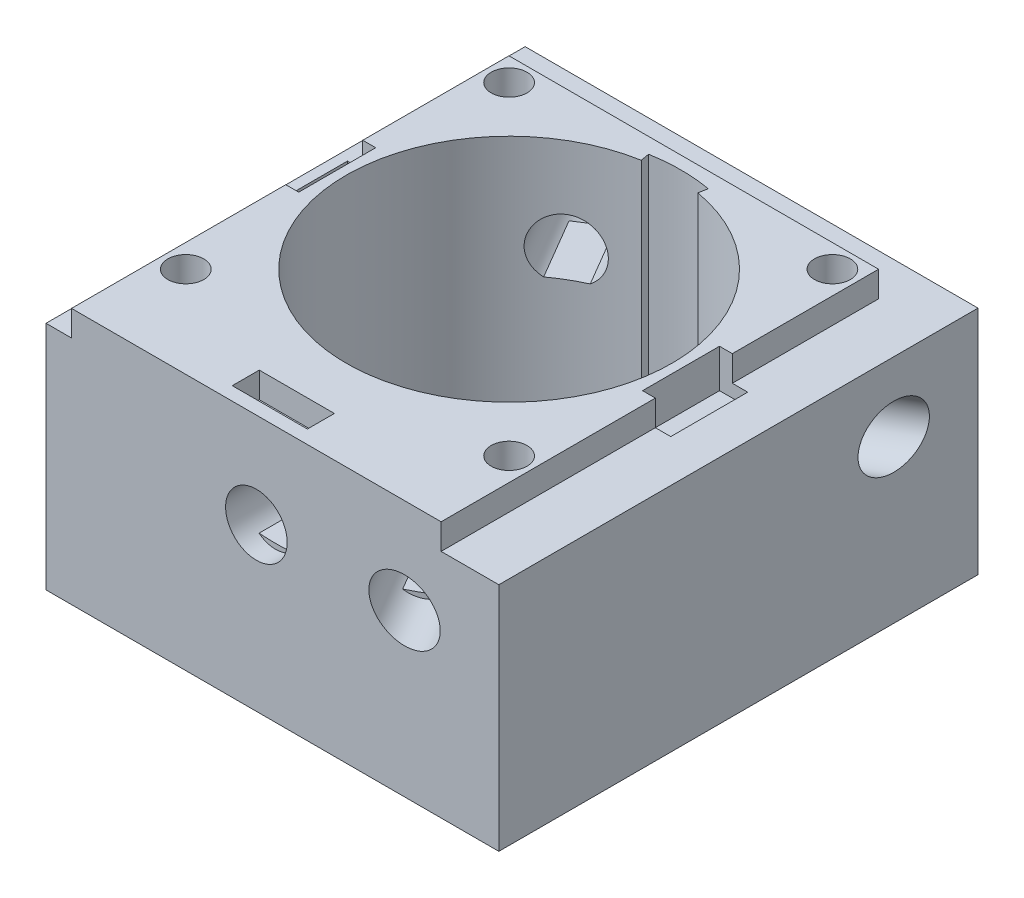
SolidWorks part; units mm, degrees
ref_plane "Front Plane" through (0, 0, 0) normal (0, 0, 1) x (1, 0, 0)
ref_plane "Top Plane" through (0, 0, 0) normal (0, 1, 0) x (1, 0, 0)
ref_plane "Right Plane" through (0, 0, 0) normal (1, 0, 0) x (0, 0, -1)
sketch "Sketch1" plane through (0, 0, 0) normal (0, 1, 0) x (1, 0, 0)
  line L1 (-20.828, 22.9235) -> (20.828, 22.9235)
  line L2 (-20.828, 22.9235) -> (-20.828, -22.9235)
  line L3 (-20.828, -22.9235) -> (20.828, -22.9235)
  line L4 (20.828, 22.9235) -> (20.828, -22.9235)
  line L5 (-20.828, 22.9235) -> (20.828, -22.9235) construction
  line L6 (-20.828, -22.9235) -> (20.828, 22.9235) construction
  point P0 (0, 0)
  dimension "D1" = 45.847
  dimension "D2" = 41.656
extrude "Boss-Extrude1" add sketch "Sketch1" along normal blind 25.4 contours L2 L1 L4 L3
sketch "Sketch2" plane through (0, 25.4, 0) normal (0, 1, 0) x (1, 0, 0)
  line L0 (0, 22.9235) -> (0, 2.0955) construction
  line L1 (-20.828, 22.9235) -> (20.828, 22.9235) construction
  circle A0 centre (0, 2.0955) radius 16.129
  dimension "D2" = 32.258
  dimension "D1" = 20.828
extrude "Cut-Extrude1" cut sketch "Sketch2" against normal up to surface (25.4 mm away) up to face at (0, 0, 0)
sketch "Sketch3" plane through (0, 25.4, 0) normal (0, 1, 0) x (1, 0, 0)
  line L0 (-18.415, 2.0955) -> (18.415, 2.0955) construction
  line L1 (0, 2.0955) -> (0, -22.9235) construction
  line L2 (17.018, -1.7145) -> (19.812, -1.7145)
  line L3 (17.018, -1.7145) -> (17.018, 5.9055)
  line L4 (17.018, 5.9055) -> (19.812, 5.9055)
  line L5 (19.812, -1.7145) -> (19.812, 5.9055)
  line L6 (17.018, -1.7145) -> (19.812, 5.9055) construction
  line L7 (17.018, 5.9055) -> (19.812, -1.7145) construction
  line L9 (-17.018, 5.9055) -> (-19.812, -1.7145) construction
  line L10 (-17.018, -1.7145) -> (-19.812, 5.9055) construction
  line L11 (-19.812, -1.7145) -> (-19.812, 5.9055)
  line L12 (-17.018, 5.9055) -> (-19.812, 5.9055)
  line L13 (-17.018, -1.7145) -> (-17.018, 5.9055)
  line L14 (-17.018, -1.7145) -> (-19.812, -1.7145)
  point P14 (0, 2.0955)
  dimension "D1" = 18.415
  dimension "D2" = 7.62
  dimension "D3" = 2.794
extrude "Cut-Extrude2" cut sketch "Sketch3" against normal blind 3.81
sketch "Sketch6" plane through (0, 25.4, 0) normal (0, 1, 0) x (1, 0, 0)
  line L0 (0, 2.0955) -> (0, 18.2245) construction
  line L1 (0, 2.0955) -> (-2.9551, 18.855)
  line L2 (0, 2.0955) -> (2.9551, 18.855)
  circle A0 centre (0, 2.0955) radius 17.018
  circle A1 centre (0, 2.0955) radius 16.129 construction
  circle M16 centre (0, 2.0955) radius 16.129
  dimension "D1" = 34.036
  dimension "D2" = 10
extrude "Cut-Extrude6" cut sketch "Sketch6" against normal up to surface (25.4 mm away) contours L2 A0 L1 M16 | L0 L2 M16 | L1 L0 M16 region at (-0.936, 25.4, -12.7937) region at (0.936, 25.4, -12.7937) region at (0, 25.4, -18.5889) up to face at (0, 0, -18.2245)
sketch "Sketch7" plane through (0, 0, 22.9235) normal (0, 0, 1) x (1, 0, 0)
  line L0 (0, 0) -> (0, 16.002) construction
  line L1 (-20.828, 0) -> (20.828, 0) construction
  circle A0 centre (0, 16.002) radius 3.048
  dimension "D2" = 6.096
  dimension "D1" = 16.002
extrude "Cut-Extrude7" cut sketch "Sketch7" against normal up to surface (9.1806 mm away) up to face at (0, 12.7, -1.973)
sketch "Sketch8" plane through (0, 25.4, 0) normal (0, 1, 0) x (1, 0, 0)
  line L1 (8.1571, -11.8187) -> (-8.1571, 16.0097) construction
  arc A0 (0, -14.0335) -> (8.1571, -11.8187) centre (0, 2.0955) cw construction
  circle A1 centre (0, 2.0955) radius 16.129 construction
sketch "Sketch9" plane through (0, 0, 0) normal (0, -1, 0) x (1, 0, 0)
  line L0 (0, -2.0955) -> (8.4098, 11.6675) construction
  circle A0 centre (0, -2.0955) radius 16.129 construction
ref_plane "Plane1" through (0.9143, 0, -0.536) normal (0.8627, 0, -0.5057) x (-0.5057, 0, -0.8627)
ref_plane "Plane2" through (-0.9143, 0, -1.5595) normal (0.5057, 0, 0.8627) x (0.8627, 0, -0.5057)
sketch "Sketch11" plane through (-0.9143, 0, -1.5595) normal (0.5057, 0, 0.8627) x (0.8627, 0, -0.5057)
  line L0 (1.0598, 0) -> (1.0598, 16.002) construction
  circle A0 centre (1.0598, 16.002) radius 3.048
  dimension "D2" = 6.096
  dimension "D1" = 16.002
sketch "Sketch12" plane through (0.9143, 0, -0.536) normal (0.8627, 0, -0.5057) x (-0.5057, 0, -0.8627)
  line L0 (1.8078, 0) -> (1.8078, 16.002) construction
  circle A0 centre (1.8078, 16.002) radius 3.048
  dimension "D2" = 6.096
  dimension "D1" = 16.002
sketch "Sketch14" plane through (0, 25.4, 0) normal (0, 1, 0) x (1, 0, 0)
  line L0 (20.828, 22.9235) -> (20.828, -22.9235) construction
  line L1 (-20.828, 22.9235) -> (20.828, 22.9235)
  line L2 (-20.828, 22.9235) -> (-20.828, 20.3835)
  line L3 (-20.828, 20.3835) -> (20.828, 20.3835)
  line L4 (20.828, 22.9235) -> (20.828, 20.3835)
  line L5 (-20.828, -22.9235) -> (20.828, -22.9235) construction
  line L6 (20.828, -22.9235) -> (18.288, -22.9235)
  line L7 (20.828, -22.9235) -> (20.828, 20.3835)
  line L8 (20.828, 20.3835) -> (18.288, 20.3835)
  line L9 (18.288, -22.9235) -> (18.288, 20.3835)
  line L10 (-20.828, 20.3835) -> (-18.3034, 20.3835)
  line L11 (-20.828, 20.3835) -> (-20.828, -22.9235)
  line L12 (-20.828, -22.9235) -> (-18.3034, -22.9235)
  line L13 (-18.3034, 20.3835) -> (-18.3034, -22.9235)
  line L15 (-3.7183, -18.9209) -> (3.7183, -18.9209)
  line L16 (-3.7183, -18.9209) -> (-3.7183, -21.5937)
  line L17 (-3.7183, -21.5937) -> (3.7183, -21.5937)
  line L18 (3.7183, -18.9209) -> (3.7183, -21.5937)
  line L19 (-3.7183, -18.9209) -> (3.7183, -21.5937) construction
  line L20 (-3.7183, -21.5937) -> (3.7183, -18.9209) construction
  point P16 (0, -20.2573)
  line M7 (-20.828, -22.9235) -> (20.828, -22.9235)
  line M8 (20.828, -22.9235) -> (20.828, 22.9235)
  line M9 (20.828, 22.9235) -> (-20.828, 22.9235)
  line M10 (-20.828, 22.9235) -> (-20.828, -22.9235)
  line M15 (17.018, 5.9055) -> (19.812, 5.9055)
  line M16 (19.812, 5.9055) -> (19.812, -1.7145)
  line M17 (19.812, -1.7145) -> (17.018, -1.7145)
  dimension "D1" = 2.54
  dimension "D2" = 2.54
  dimension "D3" = 2.5246
extrude "Cut-Extrude10" cut sketch "Sketch14" against normal blind 2.54 contours L18 L15 L16 L17 | L9 L3 M7 M8 M15 M16 M17 | L3 M10 M8 M9 | L11 L12 L13 L10 region at (0, 25.4, -21.6535) region at (20.3942, 25.4, 1.27) region at (0, 25.4, 20.2573)
sketch "Sketch17" plane through (20.828, 0, 0) normal (1, 0, 0) x (0, 0, -1)
  line L1 (-22.9235, 22.86) -> (22.9235, 22.86)
  line L2 (-22.9235, 22.86) -> (-22.9235, 0)
  line L3 (-22.9235, 0) -> (22.9235, 0)
  line L4 (22.9235, 22.86) -> (22.9235, 0)
extrude "Boss-Extrude3" add sketch "Sketch17" along normal blind 3.175
extrude "Cut-Extrude12" cut sketch "Sketch12" along normal up to surface (29.6105 mm away) up to face at (24.003, 11.43, 0)
sketch "Sketch18" plane through (0, 0, -22.9235) normal (0, 0, -1) x (-1, 0, 0)
  line L1 (-24.003, 22.86) -> (20.828, 22.86)
  line L2 (-24.003, 22.86) -> (-24.003, 0)
  line L3 (-24.003, 0) -> (20.828, 0)
  line L4 (20.828, 22.86) -> (20.828, 0)
extrude "Boss-Extrude4" add sketch "Sketch18" along normal blind 1.5875
extrude "Cut-Extrude13" cut sketch "Sketch11" against normal through all both and the other way through all
sketch "Sketch22" plane through (0, 0, 0) normal (0, -1, 0) x (1, 0, 0)
  line L0 (0, -2.0955) -> (4.9808, -24.6818)
  line L1 (0, -2.0955) -> (-4.0006, -24.8759)
  line L3 (24.003, 22.9235) -> (-20.828, 22.9235)
  line L4 (24.003, 22.9235) -> (24.003, -24.511)
  line L5 (24.003, -24.511) -> (-20.828, -24.511)
  line L6 (-20.828, 22.9235) -> (-20.828, -24.511)
  circle A0 centre (0, -2.0955) radius 16.129
  circle A1 centre (0, -2.0955) radius 23.129
  arc M11 (2.9551, -18.855) -> (-2.9551, -18.855) centre (0, -2.0955) cw
  line M12 (-2.9551, -18.855) -> (-2.8008, -17.9795)
  arc M13 (-2.8008, -17.9795) -> (2.8008, -17.9795) centre (0, -2.0955) cw
  dimension "D1" = 7
extrude "Boss-Extrude8" add sketch "Sketch22" against normal blind 13.462 contours L0 A1 L1 M11 M12 M13 region at (13.0665, 0, -12.5945)
sketch "Sketch4" plane through (0, 25.4, 0) normal (0, 1, 0) x (1, 0, 0)
  line L0 (0, 2.0955) -> (0, 22.9235) construction
  line L2 (0, 2.0955) -> (-11.5271, 2.0955) construction
  line L3 (-16.002, -13.9065) -> (16.002, -13.9065) construction
  line L4 (-16.002, -13.9065) -> (-16.002, 18.0975) construction
  line L5 (-16.002, 18.0975) -> (16.002, 18.0975) construction
  line L6 (16.002, -13.9065) -> (16.002, 18.0975) construction
  line L7 (-16.002, -13.9065) -> (16.002, 18.0975) construction
  line L8 (-16.002, 18.0975) -> (16.002, -13.9065) construction
  circle A0 centre (-16.002, -13.9065) radius 1.778
  circle A1 centre (-16.002, 18.0975) radius 1.778
  circle A2 centre (16.002, 18.0975) radius 1.778
  circle A3 centre (16.002, -13.9065) radius 1.778
  point P2 (0, 2.0955)
  dimension "D3" = 3.556
  dimension "D1" = 32.004
  dimension "D2" = 32.004
extrude "Cut-Extrude14" cut sketch "Sketch4" against normal through all
